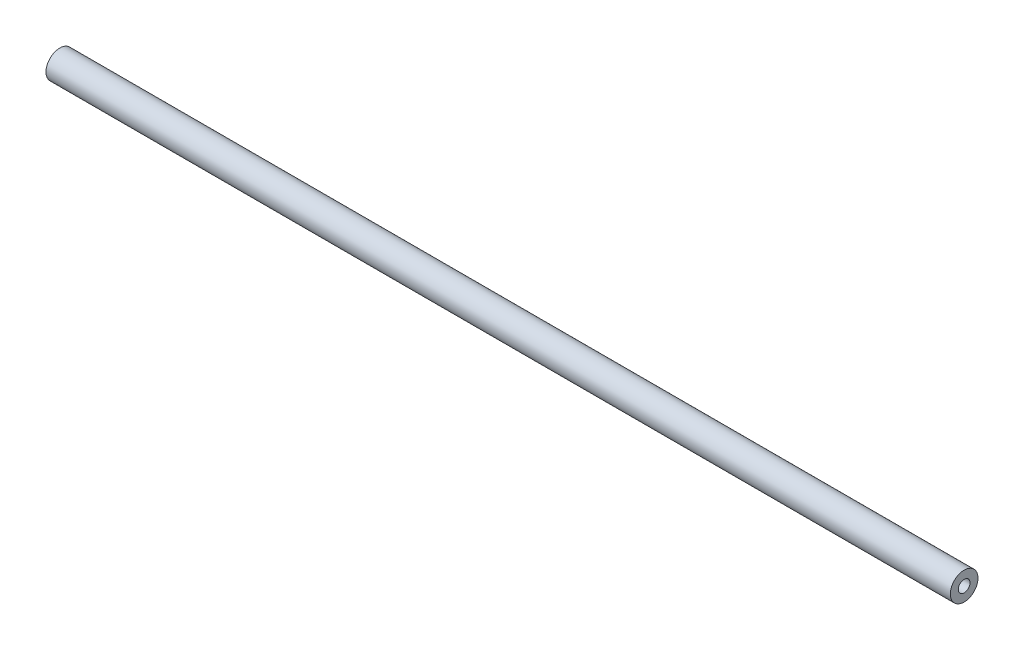
SolidWorks part; units mm, degrees
material "7075-T6 (SN)"
ref_plane "Front Plane" through (0, 0, 0) normal (0, 0, 1) x (1, 0, 0)
ref_plane "Top Plane" through (0, 0, 0) normal (0, 1, 0) x (1, 0, 0)
ref_plane "Right Plane" through (0, 0, 0) normal (1, 0, 0) x (0, 0, -1)
sketch "Sketch1" plane through (0, 0, 0) normal (1, 0, 0) x (0, 0, -1)
  circle A1 centre (0, 0) radius 4.7625
  dimension "D1" = 9.525
extrude "Boss-Extrude1" add sketch "Sketch1" along normal mid plane 311.15 contours A1 region at (0, 0, 0)
hole_wizard "#10-32 Tapped Hole1" positions "3DSketch1" profile "Sketch2" tap size "#10-32" standard "ANSI Inch"
sketch3d "3DSketch1"
  line L0 (155.575, 0, 0) -> (-155.575, 0, 0) construction
  point P0 (155.575, 0, 0)
  point P7 (-155.575, 0, 0)
sketch "Sketch2" plane through (155.575, 0, 0) normal (0, 1, 0) x (0, 0, -1)
  line L0 (0, 0) -> (0, 13.2428)
  line L1 (0, 13.2428) -> (2.0193, 12.0294)
  line L2 (2.0193, 12.0294) -> (2.0193, 0)
  line L5 (2.0193, 0) -> (0, 0)
  line L10 (0, 13.2428) -> (-2.0193, 12.0294) construction
  line L11 (0, -6.35) -> (0, 107.95) construction
  dimension "Tap Drill Dia." = 4.0386
  dimension "Tap Drill Depth" = 12.0294
  dimension "Drill Angle" = 118
cosmetic thread "Hole Thread1"
cosmetic thread "Hole Thread2"
